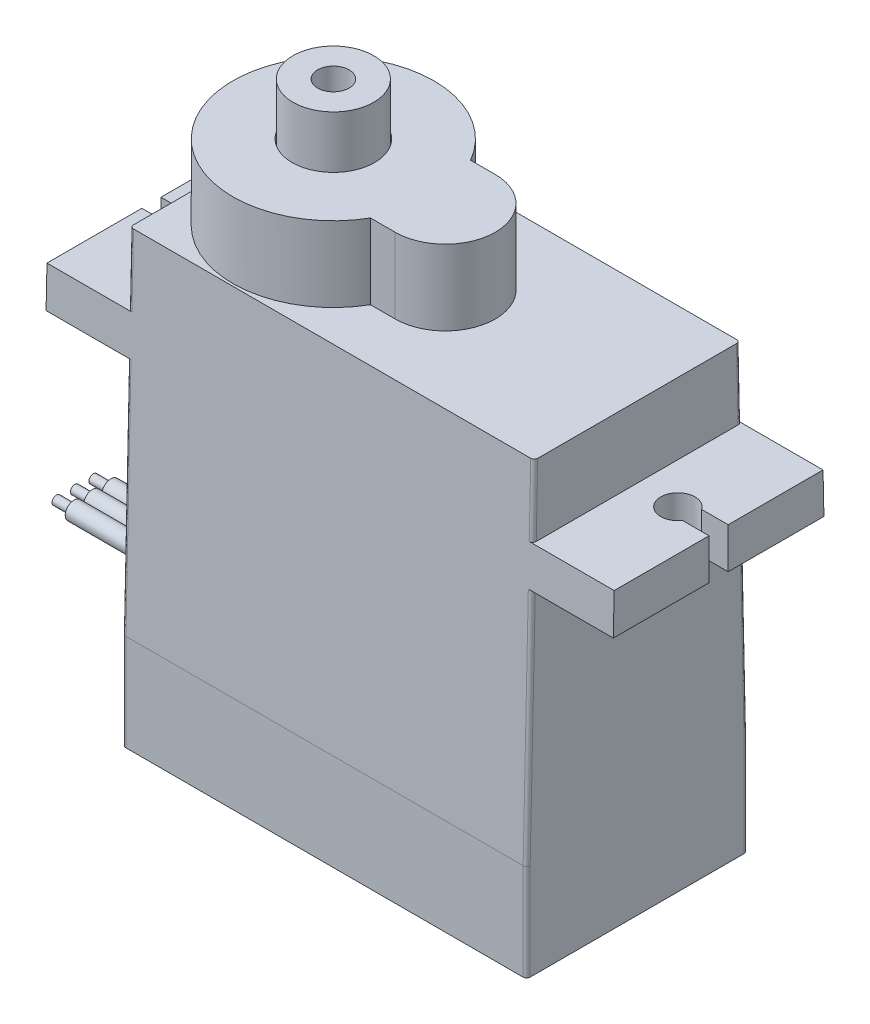
SolidWorks part; units mm, degrees
ref_plane "Front Plane" through (0, 0, 0) normal (0, 0, 1) x (1, 0, 0)
ref_plane "Top Plane" through (0, 0, 0) normal (0, 1, 0) x (1, 0, 0)
ref_plane "Right Plane" through (0, 0, 0) normal (1, 0, 0) x (0, 0, -1)
ref_axis "X-Axis" through (-88.99, 0, 0) along (1, 0, 0)
ref_axis "Y-Axis" through (0, 0, -88.99) along (0, 0, 1)
ref_axis "Z-Axis" through (0, 55, 0) along (0, -1, 0)
sketch "Sketch1" plane through (0, 0, 0) normal (0, 0, 1) x (1, 0, 0)
  line L0 (0, 0) -> (0, 10.3) construction
  line L1 (-7.13, 6.38) -> (15.9, 6.38)
  line L2 (-7.13, 6.38) -> (-7.13, 2.32)
  line L3 (-7.13, -19) -> (15.9, -19)
  line L4 (15.9, 6.38) -> (15.9, 2.32)
  line L5 (15.9, 2.32) -> (20.54, 2.32)
  line L6 (-11.77, 2.32) -> (-7.13, 2.32)
  line L7 (-11.77, 2.32) -> (-11.77, 0)
  line L8 (-11.77, 0) -> (-7.13, 0)
  line L9 (20.54, 2.32) -> (20.54, 0)
  line L10 (15.9, 0) -> (20.54, 0)
  line L11 (-7.13, 0) -> (-7.13, -19)
  line L12 (15.9, 0) -> (15.9, -19)
  line L14 (15.9, 0) -> (-7.13, 0) construction
  point P3 (4.385, 0)
  dimension "D1" = 2.32
  dimension "D2" = 32.31
  dimension "D3" = 23.03
  dimension "D4" = 4.06
  dimension "D5" = 19
  dimension "D6" = 7.13
  dimension "D7" = 15.9
  dimension "D10" = 29.3
  dimension "D11" = 4.385
extrude "Boss-Extrude1" add sketch "Sketch1" along normal mid plane 12.59
sketch "Sketch2" plane through (0, 6.38, 0) normal (0, 1, 0) x (1, 0, 0)
  line L0 (-1.405, 0) -> (4.97, 0) construction
  line L1 (3.5602, -2.85) -> (4.97, -2.85)
  line L2 (4.97, 2.85) -> (3.5602, 2.85)
  line L3 (-1.405, 0) -> (-7.13, 0) construction
  line L4 (4.97, 0) -> (7.82, 0) construction
  line L5 (-7.13, -6.295) -> (-7.13, 6.295) construction
  arc A0 (3.5602, 2.85) -> (3.5602, -2.85) centre (-1.405, 0) ccw
  arc A1 (4.97, -2.85) -> (4.97, 2.85) centre (4.97, 0) ccw
  dimension "D1" = 11.45
  dimension "D2" = 5.7
  dimension "D3" = 14.95
extrude "Boss-Extrude2" add sketch "Sketch2" along normal blind 4.28
sketch "Sketch11" plane through (-11.77, 0, 0) normal (-1, 0, 0) x (0, 0, 1)
  line L0 (-5.86, 6.38) -> (-6.295, -13.5)
  line L1 (0, 6.38) -> (-6.295, 6.38) construction
  line L2 (6.295, -19) -> (-6.295, -19) construction
  line L3 (-6.295, 0) -> (-6.295, -19) construction
  line L4 (-5.86, 6.38) -> (-6.295, 6.38)
  line L5 (-6.295, 6.38) -> (-6.295, -13.5)
  dimension "D1" = 5.86
  dimension "D2" = 5.5
extrude "Cut-Extrude4" cut sketch "Sketch11" against normal through all
mirror "Mirror1" about plane through (0, 0, 0) normal (0, 0, 1) of "Cut-Extrude4"
sketch "Sketch4" plane through (0, 0, 0) normal (0, 1, 0) x (1, 0, 0)
  line L0 (-7.13, 0) -> (-9.45, 0) construction
  line L1 (-11.77, -5.9488) -> (-11.77, 5.9488) construction
  line L2 (-10.2585, 0.545) -> (-11.77, 0.545)
  line L3 (-10.2585, 0.545) -> (-10.2585, -0.545)
  line L4 (-10.2585, -0.545) -> (-11.77, -0.545)
  line L5 (-11.77, 0.545) -> (-11.77, -0.545)
  line L8 (-9.45, 0) -> (-10.2585, 0) construction
  line L9 (-9.45, 0) -> (-11.77, 0) construction
  arc A0 (3.5602, 2.85) -> (3.5602, -2.85) centre (-1.405, 0) ccw construction
  circle A1 centre (-9.45, 0) radius 0.975
  dimension "D1" = 1.09
  dimension "D2" = 1.95
extrude "Cut-Extrude1" cut sketch "Sketch4" along normal through all contours A1 | L4 L5 L2 L3
sketch "Sketch14" plane through (0, 0.1312, 5.9967) normal (0, 0.0219, 0.9998) x (1, 0, 0)
  line L0 (4.385, -13.6345) -> (-7.13, -13.6345) construction
  line L1 (15.9, -13.6345) -> (-7.13, -13.6345) construction
ref_plane "Plane1" through (4.385, -13.5, 6.295) normal (-1, 0, 0) x (0, 0, 1)
mirror "Mirror2" about plane through (4.385, -13.5, 6.295) normal (-1, 0, 0) of "Cut-Extrude1"
sketch "Sketch5" plane through (0, -19, 0) normal (0, -1, 0) x (1, 0, 0)
  line L0 (15.9, 6.295) -> (-7.13, -6.295) construction
  line L17 (-5.49, 4.35) -> (14.26, 4.35) construction
  line L18 (-5.49, 4.35) -> (-5.49, -4.35) construction
  line L19 (-5.49, -4.35) -> (14.26, -4.35) construction
  line L20 (14.26, 4.35) -> (14.26, -4.35) construction
  line L21 (-5.49, 4.35) -> (14.26, -4.35) construction
  circle A0 centre (-5.49, 4.35) radius 1
  circle A1 centre (-5.49, -4.35) radius 1
  circle A2 centre (14.26, -4.35) radius 1
  circle A3 centre (14.26, 4.35) radius 1
  circle A4 centre (-5.49, 4.35) radius 0.975
  circle A5 centre (-5.49, -4.35) radius 0.975
  circle A6 centre (14.26, -4.35) radius 0.975
  circle A7 centre (14.26, 4.35) radius 0.975
  point P36 (4.385, 0)
  dimension "D1" = 0.025
  dimension "D4" = 1.95
  dimension "D5" = 19.75
  dimension "D6" = 8.7
extrude "Cut-Extrude2" cut sketch "Sketch5" against normal blind 1
sketch "Sketch6" plane through (-7.13, 0, 0) normal (-1, 0, 0) x (0, 0, 1)
  line L0 (-1.05, -14) -> (1.05, -14) construction
  line L1 (0, -14.5) -> (0, -19) construction
  line L3 (6.295, -19) -> (-6.295, -19) construction
  circle A0 centre (0, -14) radius 0.5
  circle A1 centre (1.05, -14) radius 0.5
  circle A2 centre (-1.05, -14) radius 0.5
  dimension "D3" = 1
  dimension "D1" = 4.5
  dimension "D2" = 2.1
extrude "Boss-Extrude4" add sketch "Sketch6" along normal blind 8
sketch "Sketch7" plane through (-15.13, 0, 0) normal (-1, 0, 0) x (0, 0, 1)
  circle A0 centre (0, -14) radius 0.25
  circle A1 centre (1.05, -14) radius 0.25
  circle A2 centre (-1.05, -14) radius 0.25
  dimension "D1" = 0.5
extrude "Boss-Extrude5" add sketch "Sketch7" along normal blind 1
sketch "Sketch3" plane through (0, 10.66, 0) normal (0, 1, 0) x (1, 0, 0)
  line L0 (4.7718, -0.52) -> (4.97, -0.52)
  line L1 (4.97, 0.52) -> (4.7718, 0.52)
  line L2 (5.49, 0) -> (7.82, 0) construction
  line L3 (-4.8, 0) -> (-7.13, 0) construction
  arc A0 (4.7718, 0.52) -> (4.7718, -0.52) centre (0, 0) ccw
  arc A1 (4.97, -0.52) -> (4.97, 0.52) centre (4.97, 0) ccw
  arc A2 (4.97, -2.85) -> (4.97, 2.85) centre (4.97, 0) ccw construction
  arc A3 (3.5602, 2.85) -> (3.5602, -2.85) centre (-1.405, 0) ccw construction
  dimension "D1" = 9.6
fillet "Fillet1" radius 0.3 4 edges at (14.26, -19, -5.325) (14.26, -19, 3.375) (-5.49, -19, -5.325) (-5.49, -19, 3.375)
fillet "Fillet3" radius 0.2 12 edges at (15.9, -16.25, -6.295) (15.9, -16.25, 6.295) (-7.13, -16.25, -6.295) (-7.13, -16.25, 6.295) (-7.13, -6.75, 6.1473) (-7.13, -6.75, -6.1473) (15.9, -6.75, 6.1473) (15.9, -6.75, -6.1473) (15.9, 4.35, -5.9044) (15.9, 4.35, 5.9044) (-7.13, 4.35, -5.9044) (-7.13, 4.35, 5.9044)
sketch "Sketch12" plane through (0, 10.66, 0) normal (0, 1, 0) x (1, 0, 0)
  circle A0 centre (-1.405, 0) radius 2.3
  circle A1 centre (-1.405, 0) radius 0.9
  dimension "D1" = 4.6
  dimension "D2" = 1.8
extrude "Boss-Extrude6" add sketch "Sketch12" along normal blind 2.95 and the other way blind 1 separate body
sketch "Sketch13" plane through (0, 13.61, 0) normal (0, 1, 0) x (1, 0, 0)
  circle A0 centre (-1.405, 0) radius 2.35
  dimension "D1" = 4.7
extrude "Cut-Extrude5" cut sketch "Sketch13" against normal blind 5
